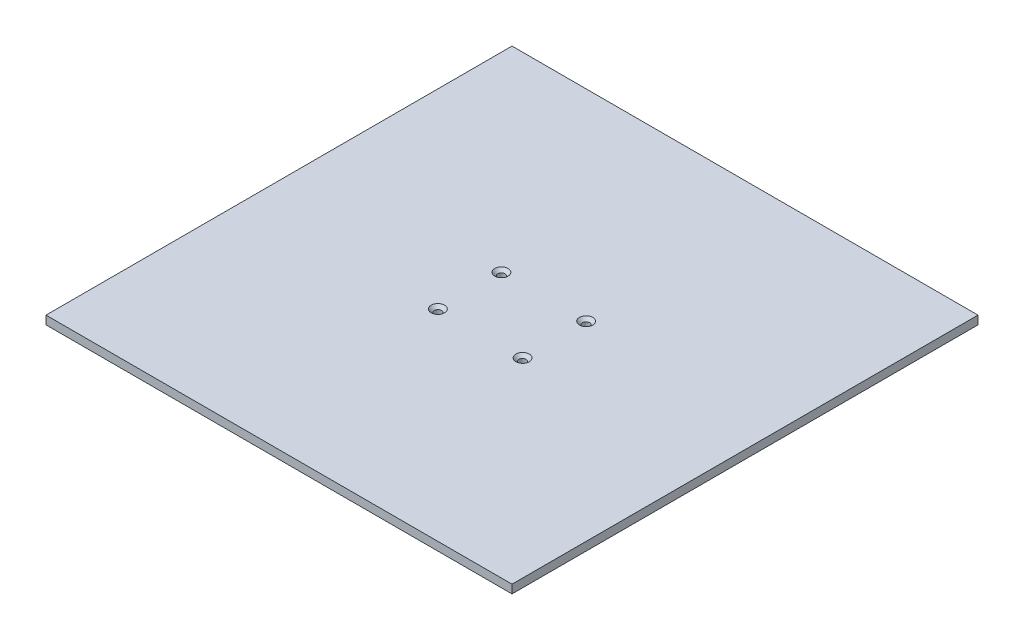
SolidWorks part; units mm, degrees
ref_plane "Front Plane" through (0, 0, 0) normal (0, 0, 1) x (1, 0, 0)
ref_plane "Top Plane" through (0, 0, 0) normal (0, 1, 0) x (1, 0, 0)
ref_plane "Right Plane" through (0, 0, 0) normal (1, 0, 0) x (0, 0, -1)
sketch "Sketch1" plane through (0, 0, 0) normal (0, 1, 0) x (1, 0, 0)
  line L1 (-110, -110) -> (110, -110)
  line L2 (-110, -110) -> (-110, 110)
  line L3 (-110, 110) -> (110, 110)
  line L4 (110, -110) -> (110, 110)
  line L5 (-110, -110) -> (110, 110) construction
  line L6 (-110, 110) -> (110, -110) construction
  point P0 (0, 0)
  dimension "D1" = 220
extrude "Boss-Extrude1" add sketch "Sketch1" along normal mid plane 4
sketch "Sketch2" plane through (0, 2, 0) normal (0, 1, 0) x (1, 0, 0)
  line L1 (-20, -15) -> (20, -15) construction
  line L2 (-20, -15) -> (-20, 15) construction
  line L3 (-20, 15) -> (20, 15) construction
  line L4 (20, -15) -> (20, 15) construction
  line L5 (-20, -15) -> (20, 15) construction
  line L6 (-20, 15) -> (20, -15) construction
  point P0 (0, 0)
  dimension "D1" = 40
  dimension "D2" = 30
hole_wizard "CSK for M3 Flat Head Machine Screw1" positions "Sketch3" profile "Sketch4" countersink size "M3" standard "ANSI Metric" end condition up to next
sketch "Sketch3" plane through (0, 2, 0) normal (0, 1, 0) x (1, 0, 0)
  point P0 (-20, 15)
  point P3 (20, 15)
  point P6 (20, -15)
  point P9 (-20, -15)
sketch "Sketch4" plane through (-20, 2, -15) normal (1, 0, 0) x (0, 0, 1)
  line L0 (0, 0) -> (0, 4)
  line L1 (0, 4) -> (1.7, 4)
  line L2 (1.7, 4) -> (1.7, 1.45)
  line L3 (1.7, 1.45) -> (3.15, 0)
  line L5 (3.15, 0) -> (0, 0)
  line L6 (-1.7, 1.45) -> (-3.15, 0) construction
  line L11 (0, -6.35) -> (0, 107.95) construction
  dimension "Thru Hole Dia." = 3.4
  dimension "Thru Hole Depth" = 4
  dimension "Near C'Sink Dia." = 6.3
  dimension "Near C'Sink Angle" = 90
